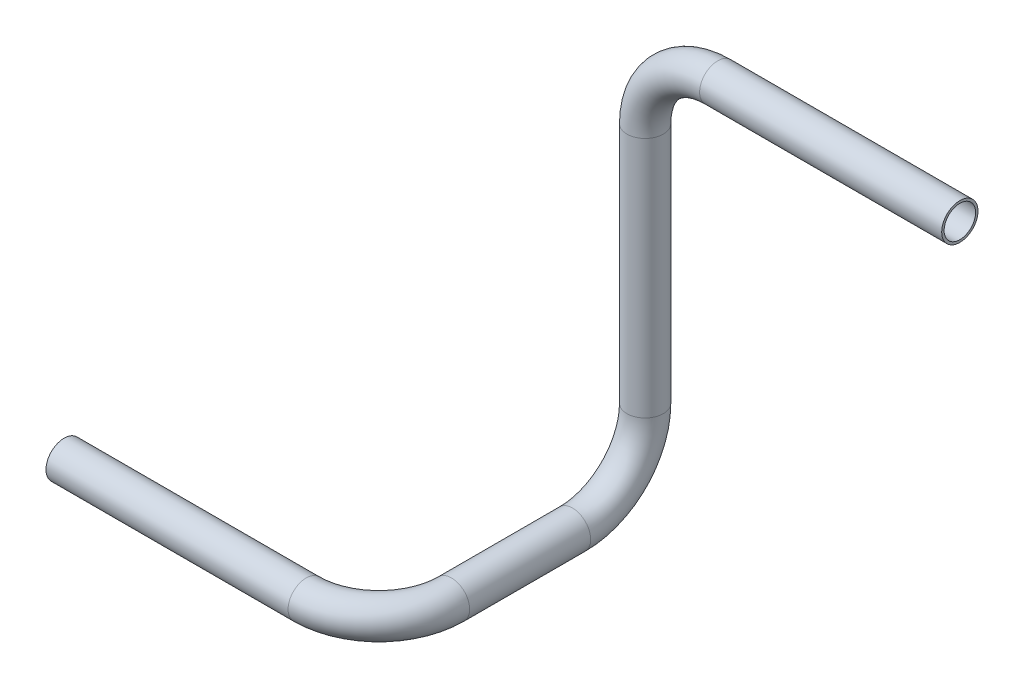
SolidWorks part; units mm, degrees
ref_plane "Front Plane" through (0, 0, 0) normal (0, 0, 1) x (1, 0, 0)
ref_plane "Top Plane" through (0, 0, 0) normal (0, 1, 0) x (1, 0, 0)
ref_plane "Right Plane" through (0, 0, 0) normal (1, 0, 0) x (0, 0, -1)
sketch3d "3DSketch1"
  line L0 (0, 0, 0) -> (200, 0, 0)
  line L1 (260, 0, -60) -> (260, 0, -160)
  line L2 (260, 60, -220) -> (260, 260, -220)
  line L3 (320, 320, -220) -> (520, 320, -220)
  arc A0 (200, 0, 0) -> (260, 0, -60) centre (200, 0, -60) ccw
  arc A1 (260, 0, -160) -> (260, 60, -220) centre (260, 60, -160) ccw
  arc A2 (260, 260, -220) -> (320, 320, -220) centre (320, 260, -220) ccw
  point P4 (200, 60, -60)
  point P8 (320, 60, -160)
  point P12 (320, 260, -280)
  dimension "D2" = 60
  dimension "D4" = 60
  dimension "D6" = 60
  dimension "D1" = 200
  dimension "D3" = 100
  dimension "D5" = 200
  dimension "D7" = 200
sweep "Sweep-Thin1" add path "3DSketch1" circular profile diameter 30 parameters "D1"=2, "D3"=30
